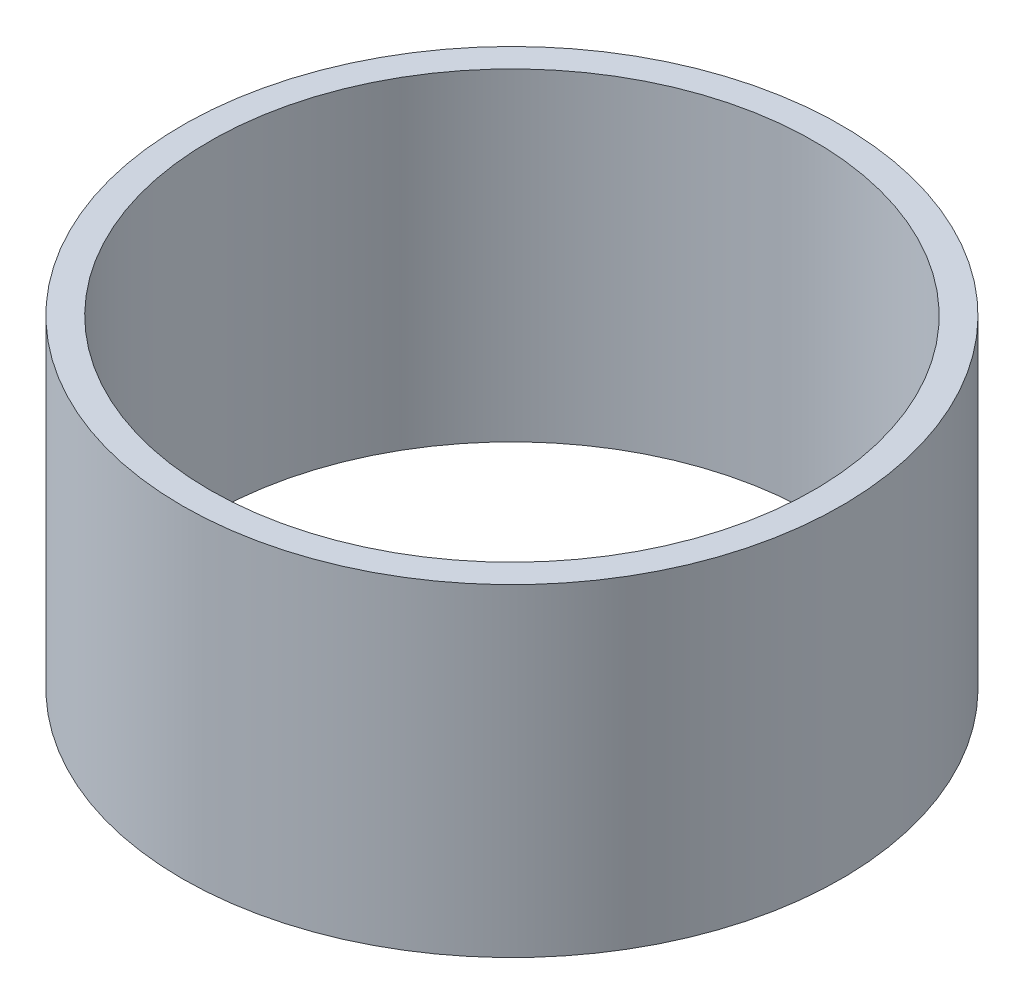
SolidWorks part; units mm, degrees
material "6061-T6 (SS)"
ref_plane "Front Plane" through (0, 0, 0) normal (0, 0, 1) x (1, 0, 0)
ref_plane "Top Plane" through (0, 0, 0) normal (0, 1, 0) x (1, 0, 0)
ref_plane "Right Plane" through (0, 0, 0) normal (1, 0, 0) x (0, 0, -1)
sketch "Sketch1" plane through (0, 0, 0) normal (0, 1, 0) x (1, 0, 0)
  circle A0 centre (0, 0) radius 76.2
  circle A1 centre (0, 0) radius 69.85
  dimension "D1" = 152.4
  dimension "D2" = 6.35
extrude "Boss-Extrude1" add sketch "Sketch1" along normal mid plane 74.676
